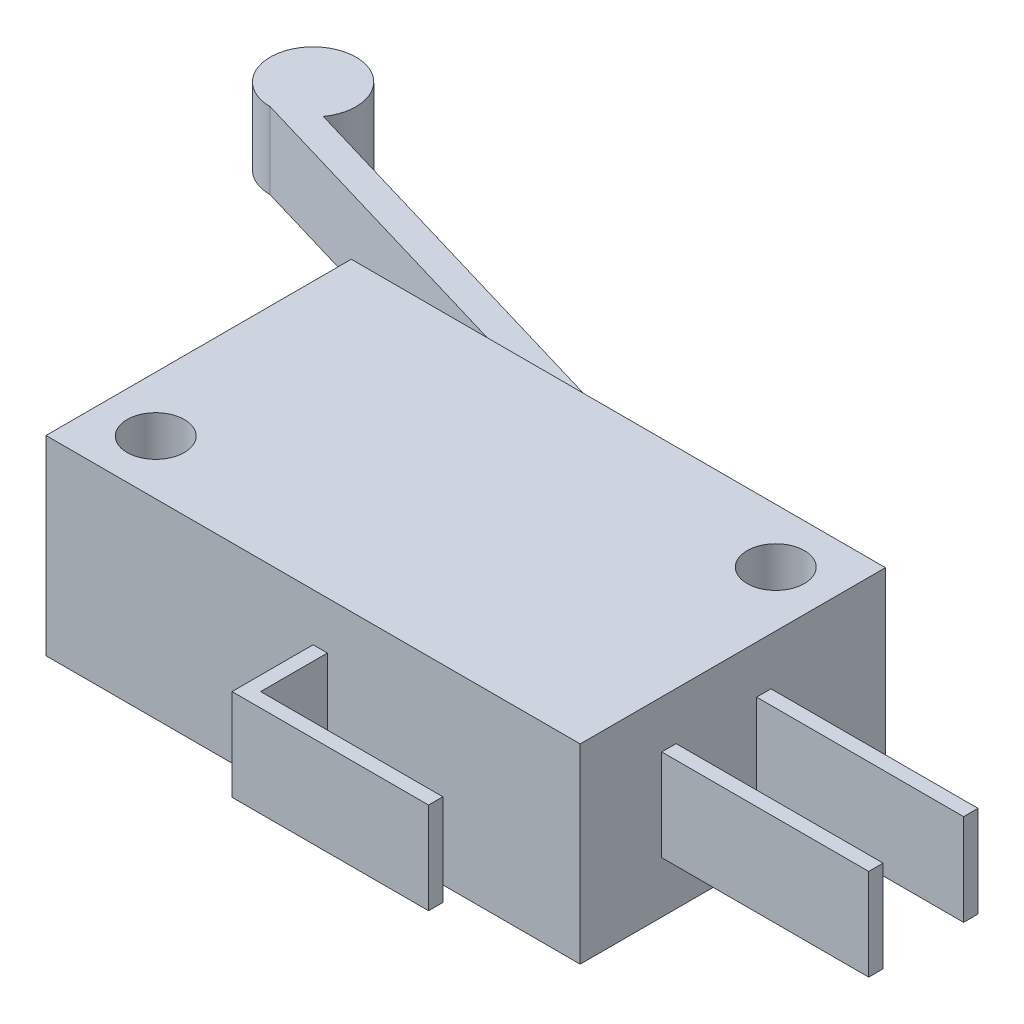
SolidWorks part; units mm, degrees
ref_plane "Front Plane" through (0, 0, 0) normal (0, 0, 1) x (1, 0, 0)
ref_plane "Top Plane" through (0, 0, 0) normal (0, 1, 0) x (1, 0, 0)
ref_plane "Right Plane" through (0, 0, 0) normal (1, 0, 0) x (0, 0, -1)
sketch "Sketch1" plane through (0, 0, 0) normal (0, 1, 0) x (1, 0, 0)
  line L0 (14, 1.4942) -> (15.43, 1.4942)
  line L1 (28, -6) -> (38.85, -6)
  line L2 (28, -6) -> (28, -6.7537)
  line L3 (28, -6.7537) -> (38.85, -6.7537)
  line L4 (38.85, -6) -> (38.85, -6.7537)
  line L5 (28, -10.9737) -> (38.85, -10.9737)
  line L6 (28, -10.9737) -> (28, -11.7275)
  line L7 (28, -11.7275) -> (38.85, -11.7275)
  line L8 (38.85, -10.9737) -> (38.85, -11.7275)
  line L9 (14.75, -19.5) -> (24.3, -19.5)
  line L11 (14, -20.25) -> (24.3, -20.25)
  line L12 (24.3, -19.5) -> (24.3, -20.25)
  line L13 (0, 0) -> (28, 0)
  line L14 (0, 0) -> (0, -16)
  line L15 (0, -16) -> (28, -16)
  line L16 (28, 0) -> (28, -16)
  line L17 (4.25, 0) -> (6.81, 0)
  line L18 (4.25, 0) -> (4.25, 2.3)
  line L19 (4.25, 2.3) -> (6.81, 2.3)
  line L20 (6.81, 0) -> (6.81, 2.3)
  line L21 (14, -20.25) -> (14, -16)
  line L22 (14.75, -19.5) -> (14.75, -16)
  line L23 (15.43, 1.4942) -> (15.43, 0)
  line L26 (-11.95, 7.7) -> (14, 0)
  line L27 (-10.114, 8.6494) -> (14, 1.4942)
  line L28 (14, 1.4942) -> (14, 0)
  circle A0 centre (2.9, -13.15) radius 1.5
  circle A1 centre (25.1, -2.85) radius 1.5
  circle A2 centre (-11.95, 9.95) radius 2.25
  point P36 (14, 0)
  dimension "D4" = 3
  dimension "D17" = 4.5
  dimension "D1" = 28
  dimension "D2" = 16
  dimension "D3" = 18.3
  dimension "D5" = 22.2
  dimension "D6" = 10.3
  dimension "D7" = 2.9
  dimension "D8" = 2.85
  dimension "D9" = 2.56
  dimension "D10" = 4.25
  dimension "D11" = 6
  dimension "D12" = 4.22
  dimension "D13" = 0.7537
  dimension "D14" = 10.85
  dimension "D15" = 9.55
  dimension "D16" = 0.75
  dimension "D18" = 3.5
  dimension "0.75" = 0.75
  dimension "D19" = 50.8
  dimension "D20" = 30.2
  dimension "D23" = 1.4324
  dimension "D21" = 1.43
extrude "Boss-Extrude1" add sketch "Sketch1" along normal blind 10 contours L16 L13 L14 L15 L6 L2 A1 A0 region at (14, 0, 8)
extrude "Boss-Extrude2" add sketch "Sketch1<3>" along normal blind 4 from offset 3.1 contours L13 L20 L19 L18 | A2 L26 L19 L20 L28 L27 | L0 L28 L13 L23 | A2 | L19 L26 L20 | A2 region at (1.5899, 0, -4.4218) region at (14.715, 0, -0.7471) region at (-11.95, 0, -9.95) region at (5.5213, 0, -1.1412) region at (6.6229, 0, -2.2445)
sketch "Sketch1<3>" plane through (0, 0, 0) normal (0, 1, 0) x (1, 0, 0) same geometry as "Sketch1"
extrude "Boss-Extrude3" add sketch "Sketch1<4>" along normal blind 4.8 from offset 2.7 contours L9 L22 L15 L21 L11 L12 | L8 L5 L6 L7 | L4 L1 L2 L3 region at (33.425, 0, 6.3769) region at (33.425, 0, 11.3506) region at (14.375, 0, 16.1114)
sketch "Sketch1<4>" plane through (0, 0, 0) normal (0, 1, 0) x (1, 0, 0) same geometry as "Sketch1"
equation "\"D7@Sketch1\"=(\"D1@Sketch1\"-\"D5@Sketch1\")/2"
equation "\"D8@Sketch1\"=(\"D2@Sketch1\"-\"D6@Sketch1\")/2"
